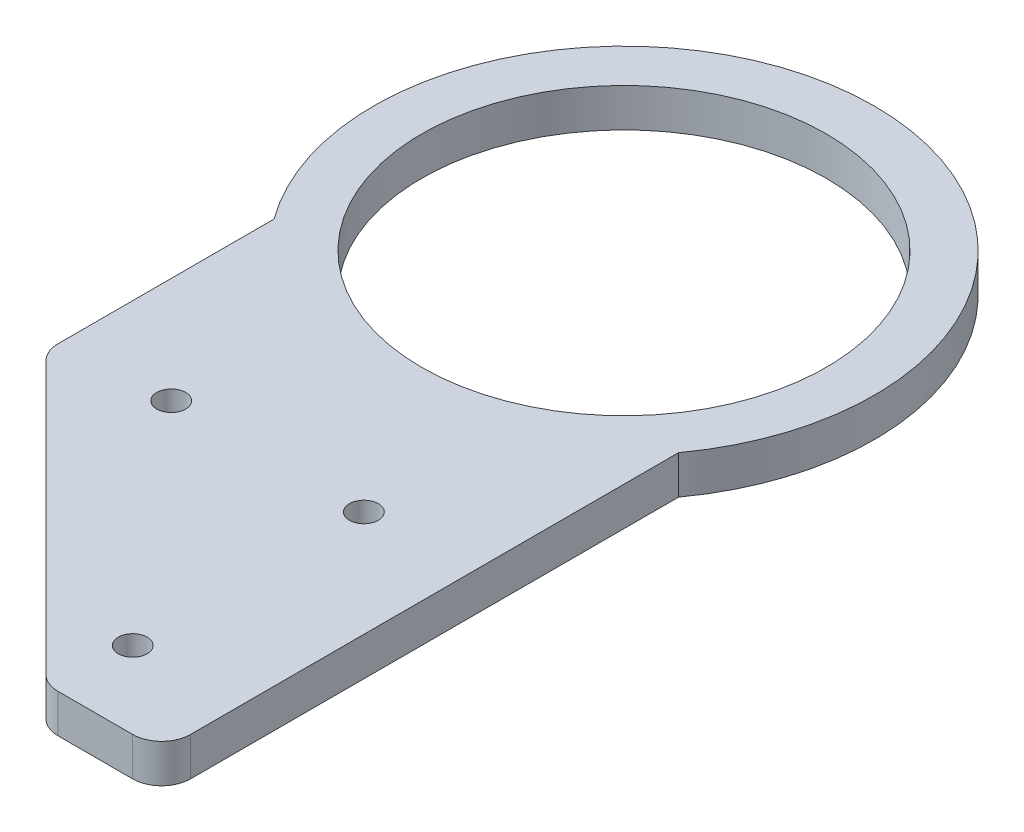
SolidWorks part; units mm, degrees
ref_plane "前视基准面" through (0, 0, 0) normal (0, 0, 1) x (1, 0, 0)
ref_plane "上视基准面" through (0, 0, 0) normal (0, 1, 0) x (1, 0, 0)
ref_plane "右视基准面" through (0, 0, 0) normal (1, 0, 0) x (0, 0, -1)
other "Configuration Table"
sketch "草图2" plane through (0, 0, 0) normal (0, 1, 0) x (1, 0, 0)
  line L0 (0, 0) -> (0, 60)
  line L1 (0, 60) -> (40, 93.9081)
  line L2 (40, 93.9081) -> (80, 60)
  line L3 (80, 60) -> (80, 0)
  line L4 (80, 0) -> (68, 0)
  line L5 (68, 0) -> (68, 42)
  line L6 (68, 42) -> (12, 42) construction
  line L7 (12, 42) -> (12, 0)
  line L8 (12, 0) -> (0, 0)
  line L9 (12, 42) -> (40, 54)
  line L10 (40, 54) -> (68, 42)
  line L11 (40, 93.9081) -> (40, 54) construction
  circle A0 centre (6, 32) radius 1.5
  circle A1 centre (6, 8) radius 1.5
  circle A2 centre (40, 69) radius 9.5
  circle A3 centre (74, 8) radius 1.5
  circle A4 centre (74, 32) radius 1.5
  dimension "D5" = 3
  dimension "D6" = 8
  dimension "D7" = 24
  dimension "D8" = 6
  dimension "D9" = 19
  dimension "D10" = 27
  dimension "D11" = 19
  dimension "D1" = 80
  dimension "D2" = 12
  dimension "D3" = 12
  dimension "D4" = 60
  dimension "D12" = 12
  dimension "D13" = 10
extrude "凸台-拉伸1" add sketch "草图2" along normal blind 4
sketch "草图4" plane through (0, 4, 0) normal (0, 1, 0) x (1, 0, 0)
  line L20 (0, 60) -> (0, 0)
  line L21 (0, 0) -> (12, 0)
  line L22 (12, 0) -> (12, 42)
  line L23 (12, 42) -> (40, 54)
  line L24 (40, 54) -> (68, 42)
  line L25 (68, 42) -> (68, 0)
  line L26 (68, 0) -> (80, 0)
  line L27 (80, 0) -> (80, 60)
  line L28 (80, 60) -> (40, 93.9081)
  line L29 (40, 93.9081) -> (0, 60)
  line L30 (0, 60) -> (0, 0)
  line L31 (0, 0) -> (12, 0)
  line L32 (12, 0) -> (12, 42)
  line L33 (12, 42) -> (40, 54)
  line L34 (40, 54) -> (68, 42)
  line L35 (68, 42) -> (68, 0)
  line L36 (68, 0) -> (80, 0)
  line L37 (80, 0) -> (80, 60)
  line L38 (80, 60) -> (40, 93.9081)
  line L39 (40, 93.9081) -> (0, 60)
  circle A2 centre (40, 69) radius 9.5
  circle A3 centre (40, 69) radius 9.5
  arc A13 (24.3672, 80.6562) -> (32.756, 50.8954) centre (40, 69) ccw
  line M22 (0, 60) -> (0, 0)
  line M24 (0, 0) -> (12, 0)
  line M26 (12, 0) -> (12, 42)
  line M28 (12, 42) -> (40, 54)
  circle M42 centre (6, 32) radius 1.5
  circle M43 centre (6, 8) radius 1.5
  dimension "D3" = 19.5
  dimension "D1" = 0
  dimension "D2" = 0
extrude "切除-拉伸1" cut sketch "草图4" against normal through all contours A13 L39 M22 M24 M26 M28 M42 M43 region at (10.0673, 4, -40.7307)
sketch "草图6" plane through (0, 4, 0) normal (0, 1, 0) x (1, 0, 0)
  line L0 (68, 0) -> (80, 0) construction
  line L1 (80, 60) -> (122, 60)
  line L2 (80, 60) -> (80, 0)
  line L3 (80, 0) -> (122, 0)
  line L4 (122, 60) -> (122, 0)
  circle A0 centre (101, 69) radius 21
  circle A1 centre (40, 69) radius 9.5 construction
  circle A2 centre (40, 69) radius 9.5
  line M13 (80, 0) -> (80, 60)
  dimension "D1" = 42
extrude "凸台-拉伸2" add sketch "草图6" against normal up to surface (4 mm away) contours A0 L1 L3 L4 M13 region at (101, 4, -26.2683) up to face at (53.2241, 0, -47.4242)
sketch "草图7" plane through (0, 4, 0) normal (0, 1, 0) x (1, 0, 0)
  line L0 (101, 48) -> (101, 0) construction
  line L1 (68, 0) -> (122, 0) construction
  circle A0 centre (91, 32) radius 1.5
  circle A1 centre (74, 32) radius 1.5 construction
  circle A2 centre (74, 32) radius 1.5
  circle A3 centre (74, 8) radius 1.5 construction
  circle A4 centre (74, 8) radius 1.5
  arc A5 (82.0263, 60) -> (119.9737, 60) centre (101, 69) ccw construction
  circle A6 centre (111, 32) radius 1.5
  circle A7 centre (111, 8) radius 1.5
  circle A8 centre (91, 8) radius 1.5
  dimension "D1" = 10
  dimension "D2" = 2
  dimension "D3" = 2
extrude "切除-拉伸2" cut sketch "草图7" against normal through all
fillet "圆角1" radius 3 8 edges at (32.756, 2, -50.8954) (40, 2, -54) (68, 2, -42) (68, 2, 0) (122, 2, 0) (80, 2, -60) (40, 2, -93.9081) (24.3672, 2, -80.6562)
extrude "切除-拉伸4" cut sketch "草图6<4>" against normal through all flip side to cut contours A0 L1 L3 L4 M13 region at (101, 4, -26.2683)
sketch "草图6<4>" plane through (0, 4, 0) normal (0, 1, 0) x (1, 0, 0) same geometry as "草图6"
sketch "草图8" plane through (0, 4, 0) normal (0, 1, 0) x (1, 0, 0)
  line L5 (82.0263, 60) -> (80, 60)
  line L6 (80, 60) -> (80, 0)
  line L7 (80, 0) -> (119, 0)
  line L8 (122, 3) -> (122, 60)
  line L9 (122, 60) -> (119.9737, 60)
  line L10 (82.0263, 60) -> (80, 60)
  line L11 (80, 60) -> (80, 0)
  line L12 (80, 0) -> (119, 0)
  line L13 (122, 3) -> (122, 60)
  line L14 (122, 60) -> (119.9737, 60)
  circle A0 centre (101, 69) radius 21
  circle A1 centre (101, 69) radius 26
  arc A2 (119, 0) -> (122, 3) centre (119, 3) ccw
  arc A3 (82.0263, 60) -> (119.9737, 60) centre (101, 69) ccw
  arc A4 (119, 0) -> (122, 3) centre (119, 3) ccw
  arc A5 (82.0263, 60) -> (119.9737, 60) centre (101, 69) ccw
  line M13 (82.0263, 60) -> (80, 60)
  line M14 (80, 60) -> (80, 0)
  line M18 (122, 60) -> (119.9737, 60)
  dimension "D2" = 5
  dimension "D1" = 0
extrude "凸台-拉伸3" add sketch "草图8" along direction (0, -1, 0) on the side against the normal up to surface (4 mm away) contours L13 A1 A0 M14 M13 M18 region at (81.0132, 4, -60.6642) up to face at (91, 0, -30.5)
sketch "草图9" plane through (0, 0, 0) normal (0, -1, 0) x (1, 0, 0)
  line L0 (110, 0) -> (80, -30)
  line L1 (80, 0) -> (119, 0) construction
  line L2 (80, 0) -> (80, -53.6703) construction
  line L3 (80, -30) -> (80, 0)
  line L4 (80, 0) -> (110, 0)
  dimension "D1" = 45
  dimension "D2" = 30
extrude "切除-拉伸5" cut sketch "草图9" against normal through all
fillet "圆角2" radius 3 2 edges at (80, 2, -30) (110, 2, 0)
